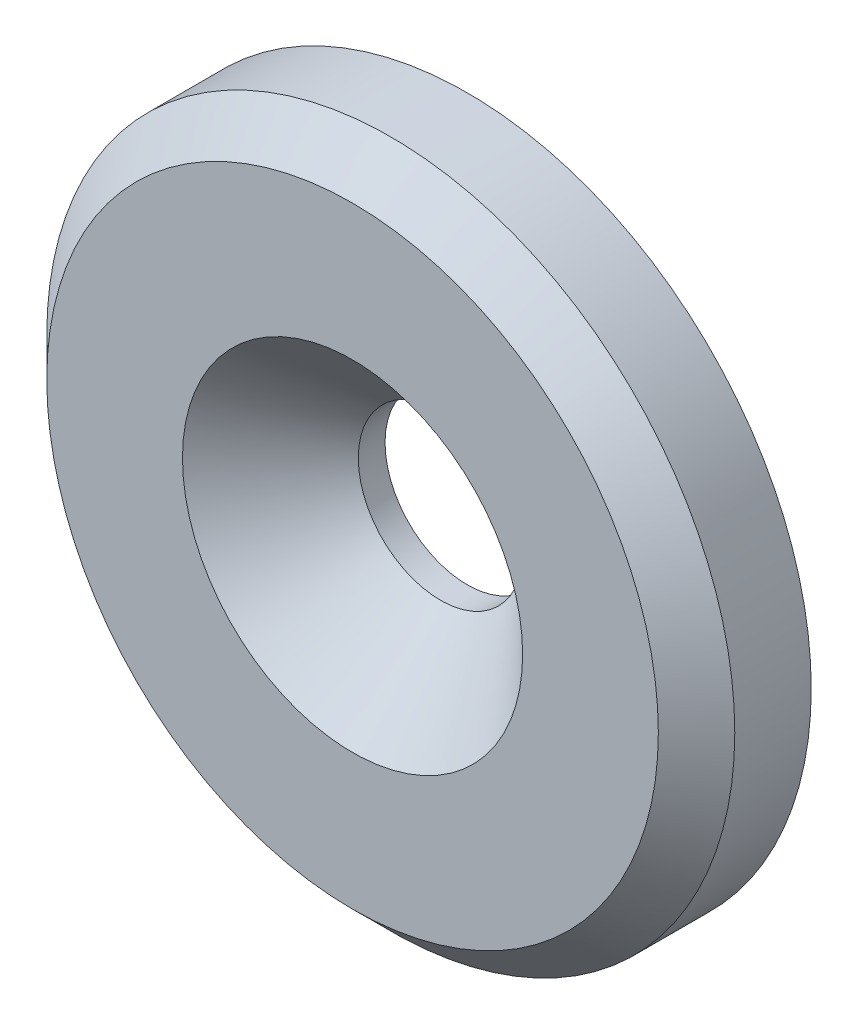
SolidWorks part; units mm, degrees
note: '?' marks a value the reader was unsure of.
ref_plane "Płaszczyzna przednia" through (0, 0, 0) normal (0, 0, 1) x (1, 0, 0)
ref_plane "Płaszczyzna górna" through (0, 0, 0) normal (0, 1, 0) x (1, 0, 0)
ref_plane "Płaszczyzna prawa" through (0, 0, 0) normal (1, 0, 0) x (0, 0, -1)
sketch "Szkic1" plane through (0, 0, 0) normal (0, 1, 0) x (1, 0, 0)
  line L0 (0, 0) -> (9, 0)
  line L1 (9, 0) -> (9, -3)
  line L2 (9, -3) -> (0, -3)
  line L3 (0, -3) -> (0, 0)
  line L4 (0, -3) -> (0, 0) construction
sketch "Szkic2" plane through (0, 0, 0) normal (0, 1, 0) x (1, 0, 0)
  line L0 (8, -3) -> (9, -3)
  line L1 (9, -3) -> (9, -2)
  line L2 (9, -2) -> (8, -3)
  line L3 (0, -3) -> (0, 0) construction
sketch "Szkic3" plane through (0, 0, 0) normal (0, 1, 0) x (1, 0, 0)
  line L0 (0, 0) -> (2.15, 0)
  line L1 (2.15, 0) -> (2.15, -0.7)
  line L2 (2.15, -0.7) -> (4.45, -3)
  line L3 (4.45, -3) -> (0, -3)
  line L4 (0, -3) -> (0, 0)
  line L5 (0, -3) -> (0, 0) construction
revolve "Obrót1" add sketch "Szkic1" angle 360 about L4
revolve "Wycięcie-obrót1" cut sketch "Szkic2" angle 360 about L3
revolve "Wycięcie-obrót2" cut sketch "Szkic3" angle 360 about L5
ref_plane "Płaszczyzna1" through (0, 0, 3) normal (0, 0, 1) x (1, 0, 0)
ref_plane "IP1 XY" through (0, 0, 3) normal (0, 0, 1) x (1, 0, 0)
ref_plane "IP1 XZ" through (0, 0, 0) normal (0, -1, 0) x (-1, 0, 0)
ref_plane "IP1 YZ" through (0, 0, 0) normal (1, 0, 0) x (0, 0, -1)
ref_axis "IP1 X" through (-80.9, 0, 3) along (1, 0, 0)?
ref_axis "IP1 Y" through (0, -50, 3) along (0, 1, 0)?
ref_axis "IP1 Z" through (0, 0, 80.9) along (0, 0, -1)?
sketch3d "IP1"
  point P0 (0, 0, 3)
ref_plane "IP2 XY" through (0, 0, 0) normal (0, 0, 1) x (1, 0, 0)
ref_plane "IP2 XZ" through (0, 0, 0) normal (0, -1, 0) x (-1, 0, 0)
ref_plane "IP2 YZ" through (0, 0, 0) normal (1, 0, 0) x (0, 0, -1)
ref_axis "IP2 X" through (-80.9, 0, 0) along (1, 0, 0)?
ref_axis "IP2 Y" through (0, -50, 0) along (0, 1, 0)?
ref_axis "IP2 Z" through (0, 0, 80.9) along (0, 0, -1)?
sketch3d "IP2"
  point P0 (0, 0, 0)
sketch "Szkic4" plane through (0, 0, 0) normal (1, 0, 0) x (0, 0, -1)
  circle A0 centre (0, 0) radius 6.75
extrude "Dodanie-wyciągnięcie1" add sketch "Szkic4" along normal blind 4.5 separate body
other "Usuń ścianę1" face at (4.5, 0, -6.75)
